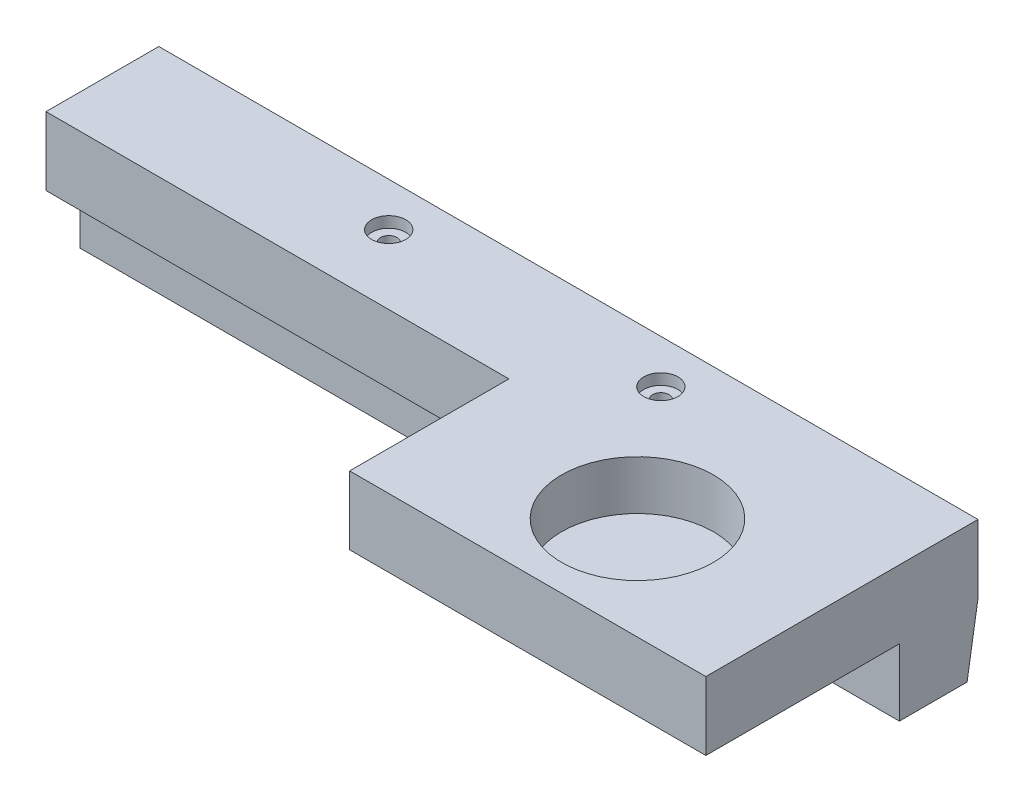
SolidWorks part; units mm, degrees
ref_plane "Płaszczyzna przednia" through (0, 0, 0) normal (0, 0, 1) x (1, 0, 0)
ref_plane "Płaszczyzna górna" through (0, 0, 0) normal (0, 1, 0) x (1, 0, 0)
ref_plane "Płaszczyzna prawa" through (0, 0, 0) normal (1, 0, 0) x (0, 0, -1)
sketch "Szkic1" plane through (0, 0, 0) normal (0, 0, 1) x (1, 0, 0)
  line L1 (-58.3066, 32.0248) -> (61.4934, 32.0248)
  line L2 (-58.3066, 32.0248) -> (-58.3066, 22.0248)
  line L3 (-58.3066, 22.0248) -> (61.4934, 22.0248)
  line L4 (61.4934, 32.0248) -> (61.4934, 22.0248)
  dimension "D1" = 119.8
  dimension "D2" = 10
extrude "Dodanie-wyciągnięcie2" add sketch "Szkic1" along normal blind 38.3 contours L2 L3 L4 L1
sketch "Szkic21" plane through (0, 32.0248, 0) normal (0, 1, 0) x (1, 0, 0)
  line L0 (61.4934, -38.3) -> (61.4934, 0) construction
  line L1 (-58.3066, 0) -> (61.4934, 0)
  line L2 (-58.3066, 0) -> (-58.3066, -10)
  line L3 (-58.3066, -10) -> (61.4934, -10)
  line L4 (61.4934, 0) -> (61.4934, -10)
extrude "Dodanie-wyciągnięcie3" add sketch "Szkic21" along normal blind 9.8
sketch "Szkic22" plane through (0, 22.0248, 0) normal (0, -1, 0) x (1, 0, 0)
  line L0 (-58.3066, 4.88) -> (-18.3066, 4.88) construction
  line L1 (-58.3066, 38.3) -> (-58.3066, 0) construction
  line L2 (-18.3066, 4.88) -> (21.4934, 4.88) construction
  line L3 (21.4934, 4.88) -> (61.4934, 4.88) construction
  line L4 (61.4934, 38.3) -> (61.4934, 0) construction
  line L5 (1.9729, 4.88) -> (1.9729, 0) construction
  line L6 (-58.3066, 0) -> (61.4934, 0) construction
hole_wizard "Pogłębienie walcowe pod M2 wkręt do części metalowych z łbem stożkowym ściętym2" positions "Szkic23" profile "Szkic24" counterbore size "M2" standard "Ansi Metric" end condition through all
sketch "Szkic23" plane through (0, 22.0248, 0) normal (0, -1, 0) x (-1, 0, 0)
  point P0 (-21.4934, -4.88)
  point P3 (18.3066, -4.88)
sketch "Szkic24" plane through (21.4934, 22.0248, 4.88) normal (1, 0, 0) x (0, 0, -1)
  line L0 (0, 0) -> (0, 19.8)
  line L1 (0, 19.8) -> (1.2, 19.8)
  line L3 (1.2, 19.8) -> (1.2, 1.6)
  line L4 (1.2, 1.6) -> (2.5, 1.6)
  line L5 (2.5, 1.6) -> (2.5, 0)
  line L7 (2.5, 0) -> (0, 0)
  line L11 (0, -6.35) -> (0, 107.95) construction
  dimension "Średnica otworu na wylot" = 2.4
  dimension "Głębokość otworu na wylot" = 19.8
  dimension "Średnica pogłębienia walcowego" = 5
  dimension "Głębokość pogłębienia walcowego" = 1.6
sketch "Szkic28" plane through (0, 22.0248, 0) normal (0, -1, 0) x (1, 0, 0)
  line L0 (36.4934, 0) -> (36.4934, 23.3) construction
  line L1 (-58.3066, 0) -> (61.4934, 0) construction
  line L2 (36.4934, 23.3) -> (61.4934, 23.3) construction
  line L3 (61.4934, 38.3) -> (61.4934, 0) construction
  line L4 (-58.3066, 38.3) -> (61.4934, 38.3) construction
  circle A0 centre (36.4934, 23.3) radius 11.1
  dimension "D1" = 15
extrude "Wytnij-wyciągnięcie1" cut sketch "Szkic28" against normal blind 7.2
sketch "Szkic31" plane through (61.4934, 0, 0) normal (1, 0, 0) x (0, 0, -1)
  line L0 (-10, 32.0248) -> (-10, 71.9248)
  line L2 (0, 41.2325) -> (0, 32.0248)
  line L6 (0, 41.8248) -> (0, 22.0248) construction
  line L8 (0, 32.0248) -> (1.5, 32.0248)
  line L10 (-10, 32.0248) -> (1.5, 32.0248)
  line L12 (-10, 71.9248) -> (-5, 71.9248)
  line L13 (-5, 71.9248) -> (1.5, 32.0248)
  line L14 (-0.4105, 43.7521) -> (0.2752, 39.543)
  line L15 (0.2752, 39.543) -> (3.3905, 40.0505)
  line L16 (3.3905, 40.0505) -> (-0.4105, 43.7521)
  line M5 (0, 22.0248) -> (0, 41.8248)
  line M6 (0, 41.8248) -> (-10, 41.8248)
extrude "Wytnij-wyciągnięcie4" cut sketch "Szkic31" against normal blind 124.8 contours L13 M6 M5 region at (61.4934, 41.6274, 0.0322)
extrude "Dodanie-wyciągnięcie5" add sketch "Szkic31<5>" against normal blind 119.8 contours L13 L8 M5 region at (61.4934, 35.0941, -0.5)
sketch "Szkic31<5>" plane through (61.4934, 0, 0) normal (1, 0, 0) x (0, 0, -1) same geometry as "Szkic31"
sketch "Szkic34" plane through (0, 0, 0) normal (0, 0, -1) x (-1, 0, 0)
  line L1 (-61.4934, 32.0248) -> (58.3066, 32.0248)
  line L2 (-61.4934, 32.0248) -> (-61.4934, 22.0248)
  line L3 (-61.4934, 22.0248) -> (58.3066, 22.0248)
  line L4 (58.3066, 32.0248) -> (58.3066, 22.0248)
extrude "Dodanie-wyciągnięcie6" add sketch "Szkic34" along normal blind 1.5
sketch "Szkic37" plane through (0, 32.0248, 0) normal (0, 1, 0) x (1, 0, 0)
  line L1 (61.4934, -38.3) -> (9.3934, -38.3)
  line L2 (61.4934, -38.3) -> (61.4934, -30)
  line L3 (61.4934, -30) -> (9.3934, -30)
  line L4 (9.3934, -38.3) -> (9.3934, -30)
mirror "Lustro2" about plane through (-58.3066, 22.0248, 38.3) normal (0, 1, 0) of bodies 125 144
move or copy body "Obiekt-Przenieś/Kopiuj1" bodies to move or copy 146 copy no translate (0, -36.7663, 0) parameters "D1"=0, "D2"=36.7663, "D3"=0
delete or keep bodies "Obiekt-Usuń/zachowaj 1" type delete bodies bodies 125
sketch "Szkic38" plane through (0, 0, 38.3) normal (0, 0, 1) x (1, 0, 0)
  line L0 (-58.3066, -24.7414) -> (61.4934, -24.7414) construction
  line L1 (-58.3066, -14.7414) -> (9.3934, -14.7414)
  line L2 (-58.3066, -14.7414) -> (-58.3066, -24.7414)
  line L3 (-58.3066, -24.7414) -> (9.3934, -24.7414)
  line L4 (9.3934, -14.7414) -> (9.3934, -24.7414)
extrude "Wytnij-wyciągnięcie5" cut sketch "Szkic38" against normal blind 23.3
